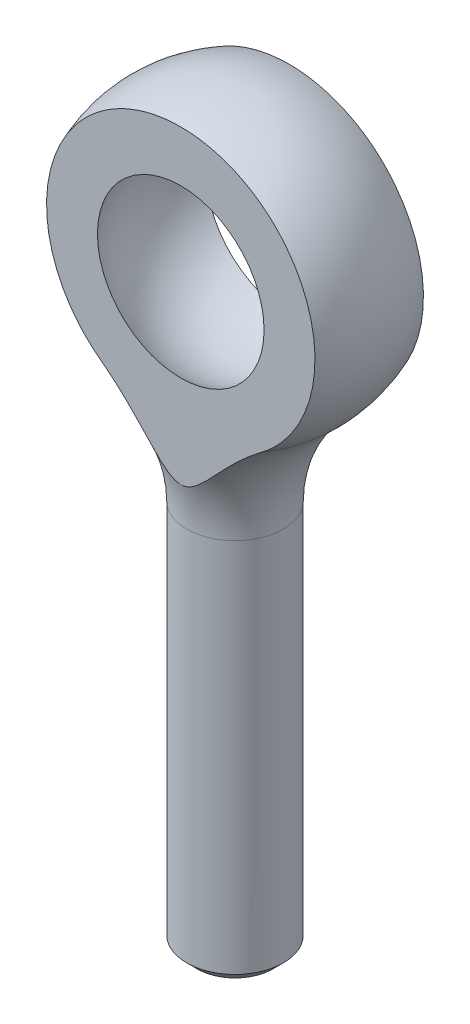
SolidWorks part; units mm, degrees
material "AISI 1045 Steel, cold drawn"
ref_plane "Front" through (0, 0, 0) normal (0, 0, 1) x (1, 0, 0)
ref_plane "Top" through (0, 0, 0) normal (0, 1, 0) x (1, 0, 0)
ref_plane "Right" through (0, 0, 0) normal (1, 0, 0) x (0, 0, -1)
sketch "Sketch1" plane through (0, 0, 0) normal (0, 0, 1) x (1, 0, 0)
  line L0 (0, 0) -> (0, -25.4)
  line L1 (0, -25.4) -> (3.175, -25.4)
  line L2 (3.175, -25.4) -> (3.175, 0)
  line L3 (3.175, 0) -> (0, 0)
  line L5 (0, 23.8125) -> (0, 0) construction
  line L6 (0, 23.8125) -> (9.525, 23.8125) construction
  line L7 (9.525, 23.8125) -> (9.525, 14.2875) construction
  line L8 (-3.175, -25.4) -> (-3.175, 0) construction
  arc A0 (6.3827, 7.2174) -> (0, 23.8125) centre (0, 14.2875) ccw construction
  circle A1 centre (0, 14.2875) radius 3.175 construction
  circle A2 centre (0, 14.2875) radius 6.35 construction
  circle A3 centre (0, 14.2875) radius 6.5405 construction
  arc A4 (3.175, 0) -> (6.3827, 7.2174) centre (12.8984, 0) cw construction
  dimension "A" = 6.35
  dimension "Ball Dia" = 12.7
  dimension "B" = 19.05
  dimension "D1" = 13.081
  dimension "D" = 39.6875
  dimension "E" = 25.4
  dimension "Thread Dia" = 6.35
revolve "Revolve1" add sketch "Sketch1" angle 360 about L5
chamfer "Chamfer2" distance 0.6804 angle 45 1 edges at (-3.175, -25.4, 0)
sketch "Sketch21" plane through (0, 0, 0) normal (0, 1, 0) x (1, 0, 0)
  circle A1 centre (0, 0) radius 3.175
  circle A2 centre (0, 0) radius 3.175
  dimension "D1" = 0
curve "Helix/Spiral1" [suppressed] pitch 0.9071 height 29.2608 turns 32.256 parameters "Thread Pitch"=0.9071
sketch "Sketch22" plane through (0, 0, 0) normal (0, 0, 1) x (1, 0, 0)
  line L0 (3.175, 0.7938) -> (3.175, 0)
  line L1 (3.175, 0) -> (2.5858, 0.3402)
  line L2 (2.5858, 0.3402) -> (2.5858, 0.4536)
  line L3 (2.5858, 0.4536) -> (3.175, 0.7938)
  line L4 (2.8804, 0.6237) -> (2.8804, 0.1701) construction
  dimension "D1" = 0.4536
  dimension "D2" = 0.1134
  dimension "D3" = 60
sweep "Cut-Sweep1" [suppressed] cut profiles "Sketch22" path "Helix/Spiral1"
sketch "Sketch4" plane through (0, 0, 0) normal (0, 0, 1) x (1, 0, 0)
  line L0 (3.175, 0) -> (0, 0) construction
  line L1 (0, 7.747) -> (0, 0)
  line L2 (0, 23.8125) -> (0, 0) construction
  line L3 (3.175, 0) -> (0, 0)
  line L5 (0, 23.8125) -> (0, 20.828)
  line L6 (0, 23.8125) -> (0, 26.3525) construction
  arc A0 (6.3827, 7.2174) -> (0, 23.8125) centre (0, 14.2875) ccw construction
  arc A1 (6.3827, 7.2174) -> (0, 23.8125) centre (0, 14.2875) ccw
  arc A2 (6.3827, 7.2174) -> (3.175, 0) centre (12.8984, 0) ccw construction
  arc A3 (6.3827, 7.2174) -> (3.175, 0) centre (12.8984, 0) ccw
  circle A4 centre (0, 14.2875) radius 6.5405 construction
  arc A5 (0, 7.747) -> (0, 20.828) centre (0, 14.2875) ccw
  dimension "D1" = 2.54
revolve "Revolve2" add sketch "Sketch4" angle 360 about L6
sketch "Sketch5" plane through (0, 0, 0) normal (1, 0, 0) x (0, 0, -1)
  line L0 (3.5687, 23.8125) -> (9.525, 23.8125)
  line L1 (-3.5687, 23.8125) -> (3.5687, 23.8125) construction
  line L2 (-3.5687, 23.8125) -> (-3.5687, 1.4275)
  line L3 (-3.175, 0) -> (3.175, 0) construction
  line L4 (3.5687, 23.8125) -> (3.5687, 1.4275)
  line L5 (9.525, 23.8125) -> (9.525, 0)
  line L6 (9.525, 0) -> (3.175, 0)
  line L7 (-3.175, 0) -> (-9.525, 0)
  line L8 (-9.525, 0) -> (-9.525, 23.8125)
  line L9 (-9.525, 23.8125) -> (-3.5687, 23.8125)
  line L10 (3.175, 0) -> (3.5687, 1.4275)
  line L11 (-3.175, 0) -> (-3.5687, 1.4275)
  line L12 (-3.5687, 1.4275) -> (3.5687, 1.4275) construction
  line L13 (0, 0) -> (0, 1.4275) construction
  arc A0 (6.3827, 7.2174) -> (-6.3827, 7.2174) centre (0, 14.2875) ccw construction
  dimension "F" = 7.1374
  dimension "D2" = 1.4275
  dimension "D1" = 6.35
extrude "Cut-Extrude1" cut sketch "Sketch5" against normal through all and the other way through all
sketch "Sketch7" plane through (0, 0, 0) normal (0, 0, 1) x (1, 0, 0)
  line L0 (0, 20.6375) -> (0, 7.9375)
  line L1 (0, 23.8125) -> (0, 0) construction
  line L2 (0, 0) -> (0, 7.9375) construction
  arc A0 (0, 7.9375) -> (0, 20.6375) centre (0, 14.2875) ccw
  circle A1 centre (0, 14.2875) radius 6.35 construction
revolve "Revolve3" [suppressed] add sketch "Sketch7" angle 360 about L2
sketch "Sketch8" plane through (0, 0, 0) normal (1, 0, 0) x (0, 0, -1)
  line L0 (-3.5687, 23.8125) -> (3.5687, 23.8125) construction
  line L1 (-4.7625, 23.8125) -> (4.7625, 23.8125) construction
  line L2 (-4.7625, 23.8125) -> (-4.7625, 0)
  line L3 (-4.7625, 0) -> (4.7625, 0) construction
  line L4 (4.7625, 23.8125) -> (4.7625, 0)
  line L5 (4.7625, 23.8125) -> (9.525, 23.8125)
  line L6 (9.525, 23.8125) -> (9.525, 0)
  line L7 (9.525, 0) -> (4.7625, 0)
  line L8 (-4.7625, 0) -> (-9.525, 0)
  line L9 (-9.525, 0) -> (-9.525, 23.8125)
  line L10 (-9.525, 23.8125) -> (-4.7625, 23.8125)
  dimension "C" = 9.525
extrude "Cut-Extrude3" [suppressed] cut sketch "Sketch8" against normal through all and the other way through all
sketch "Sketch10" plane through (0, 0, 0) normal (0, 0, 1) x (1, 0, 0)
  circle A0 centre (0, 14.2875) radius 3.175 construction
  circle A1 centre (0, 14.2875) radius 3.175
extrude "Cut-Extrude4" [suppressed] cut sketch "Sketch10" against normal through all and the other way through all
chamfer "Chamfer1" [suppressed] distance 0.3175 angle 45
sketch "Sketch12" [suppressed] plane through (0, 0, 0) normal (1, 0, 0) x (0, 0, -1)
  line L1 (4.7625, 14.2875) -> (-26.1874, 14.2875) construction
  line L2 (4.7625, 14.2875) -> (4.7625, 11.1125) construction
  line L3 (-13.4874, 11.1125) -> (4.7625, 11.1125) construction
  line L4 (-26.1874, 14.2875) -> (-26.1874, 11.1125)
  line L5 (4.7625, 10.0874) -> (4.7625, 18.4876) construction
  line L6 (4.7625, 14.2875) -> (7.9375, 14.2875) construction
  line L14 (0, 11.1125) -> (0, 14.2875) construction
  line L15 (0, 23.8125) -> (0, 0) construction
  line L20 (4.7625, 17.4625) -> (-26.1874, 17.4625) construction
  line L21 (-13.4874, 11.1125) -> (-13.4874, 17.4625) construction
  line L22 (-11.9126, 11.1125) -> (-11.9126, 17.4625) construction
  line L23 (-13.4874, 11.1125) -> (-13.4874, 14.2875)
  line L24 (-13.4874, 11.1125) -> (-26.1874, 11.1125)
  line L25 (-13.4874, 14.2875) -> (-26.1874, 14.2875)
  dimension "L Length" = 26.1874
  dimension "S Thread Length" = 12.7
  dimension "P Length" = 14.2748
revolve "Revolve4" [suppressed] add sketch "Sketch12" angle 360 about L6
chamfer "Chamfer3" [suppressed] distance 0.6804 angle 45
sketch "Sketch23" [suppressed] plane through (0, 0, 13.4874) normal (0, 0, -1) x (-1, 0, 0)
  circle A1 centre (0, 14.2875) radius 3.175
  circle A2 centre (0, 14.2875) radius 3.175
  dimension "D1" = 0
curve "Helix/Spiral2" [suppressed] pitch 0.9071 height 15.875 turns 17.5 parameters "Thread Pitch"=0.9071
sketch "Sketch24" [suppressed] plane through (0, 0, 0) normal (1, 0, 0) x (0, 0, -1)
  line L0 (-13.4874, 17.4625) -> (-12.6937, 17.4625)
  line L1 (-12.6937, 17.4625) -> (-13.0338, 16.8733)
  line L2 (-13.0338, 16.8733) -> (-13.1472, 16.8733)
  line L3 (-13.1472, 16.8733) -> (-13.4874, 17.4625)
  line L4 (-13.3173, 17.1679) -> (-12.8637, 17.1679) construction
  dimension "D1" = 60
  dimension "D2" = 0.4536
  dimension "D3" = 0.1134
sweep "Cut-Sweep2" [suppressed] cut profiles "Sketch24" path "Helix/Spiral2"
sketch "Sketch15" [suppressed] plane through (0, 0, 0) normal (1, 0, 0) x (0, 0, -1)
  line L0 (4.7625, 14.2875) -> (7.9375, 14.2875) construction
  line L1 (-13.4874, 14.2875) -> (4.7625, 14.2875)
  line L2 (-13.4874, 14.2875) -> (-13.4874, 11.1125)
  line L3 (-13.4874, 11.1125) -> (4.7625, 11.1125)
  line L4 (4.7625, 14.2875) -> (4.7625, 11.1125)
  line L5 (4.7625, 14.2875) -> (7.9375, 14.2875) construction
revolve "Revolve5" [suppressed] add sketch "Sketch15" angle 360 about L5
ref_plane "Plane1" [suppressed] through (0, 0, 11.9126) normal (0, 0, 1) x (1, 0, 0)
sketch "Sketch16" [suppressed] plane through (0, 0, 11.9126) normal (0, 0, 1) x (1, 0, 0)
  line L1 (0, 18.3203) -> (-3.4925, 16.3039)
  line L2 (-3.4925, 16.3039) -> (-3.4925, 12.2711)
  line L3 (-3.4925, 12.2711) -> (0, 10.2547)
  line L4 (0, 10.2547) -> (3.4925, 12.2711)
  line L5 (3.4925, 12.2711) -> (3.4925, 16.3039)
  line L6 (3.4925, 16.3039) -> (0, 18.3203)
  circle A0 centre (0, 14.2875) radius 3.4925 construction
  dimension "D1" = 6.985
extrude "Extrude1" [suppressed] add sketch "Sketch16" against normal blind 4.5357
sketch "Sketch17" [suppressed] plane through (0, 0, 11.9126) normal (0, 0, 1) x (1, 0, 0)
  circle A0 centre (0, 14.2875) radius 3.4925 construction
  circle A1 centre (0, 14.2875) radius 3.4925
extrude "Cut-Extrude5" [suppressed] cut sketch "Sketch17" against normal through all draft 60 flip side to cut
sketch "Sketch18" [suppressed] plane through (0, 0, 7.3769) normal (0, 0, -1) x (-1, 0, 0)
  circle A0 centre (0, 14.2875) radius 3.4925 construction
  circle A1 centre (0, 14.2875) radius 3.4925
extrude "Cut-Extrude6" [suppressed] cut sketch "Sketch18" against normal through all draft 60 flip side to cut
sketch "Sketch20" [suppressed] plane through (0, 0, 0) normal (1, 0, 0) x (0, 0, -1)
  line L0 (-4.8895, 18.4876) -> (-5.9146, 17.4625)
  line L1 (-5.9146, 17.4625) -> (-4.8895, 17.4625)
  line L2 (-4.8895, 17.4625) -> (-4.8895, 18.4876)
  line L4 (-4.7625, 18.4876) -> (-4.8895, 18.4876) construction
  line L5 (4.7625, 17.4625) -> (-7.3769, 17.4625) construction
  line L6 (-4.7625, 18.4876) -> (-4.7625, 10.0874) construction
  line L7 (4.7625, 14.2875) -> (-26.1874, 14.2875) construction
  line L8 (4.7625, 14.2875) -> (-26.1874, 14.2875) construction
  arc A0 (4.7625, 18.4876) -> (-4.7625, 18.4876) centre (0, 14.2875) ccw construction
  dimension "D1" = 0.127
  dimension "D2" = 45
revolve "Revolve6" [suppressed] add sketch "Sketch20" angle 360 about L8
sketch "Sketch11" [suppressed] plane through (0, 0, 0) normal (1, 0, 0) x (0, 0, -1)
  line L0 (0, 14.2875) -> (-5.9146, 17.0455) construction
  line L2 (0, 14.2875) -> (-5.9146, 11.5295) construction
  line L3 (0, 23.8125) -> (0, 0) construction
  line L4 (-5.9146, 17.4625) -> (-5.9146, 11.1125) construction
  line L5 (0, 14.2875) -> (0.4604, 14.5022) construction
  line L6 (0, 14.2875) -> (0.4604, 14.0728) construction
  dimension "D2" = 0.508
  dimension "Swivel" = 50
equation "\"D1@Sketch1\"=\"Ball Dia@Sketch1\"*1.03"
equation "\"D1@Chamfer1\"=\"A@Sketch1\"/20"
equation "\"D1@Sketch5\"=\"Thread Dia@Sketch1\""
equation "\"D2@Sketch5\"=\"F@Sketch5\"/5"
equation "\"D1@Sketch16\"=\"A@Sketch1\"*1.1"
equation "\"D1@Extrude1\"= \"Thread Pitch@Helix/Spiral2\"*5"
equation "\"D3@Helix/Spiral1\" = \"E@Sketch1\" + .152"
equation "\"D1@Sketch22\" = \"Thread Pitch@Helix/Spiral1\" * .5"
equation "\"D2@Sketch22\" = \"Thread Pitch@Helix/Spiral1\" * .125"
equation "\"D1@Chamfer2\" = \"Thread Pitch@Helix/Spiral1\" * .75"
equation "\"D3@Helix/Spiral2\" = \"S Thread Length@Sketch12\" + .125"
equation "\"D2@Sketch24\" = \"Thread Pitch@Helix/Spiral2\" * .5"
equation "\"D3@Sketch24\" = \"Thread Pitch@Helix/Spiral2\" * .125"
equation "\"D1@Chamfer3\" = \"Thread Pitch@Helix/Spiral2\" * .75"
